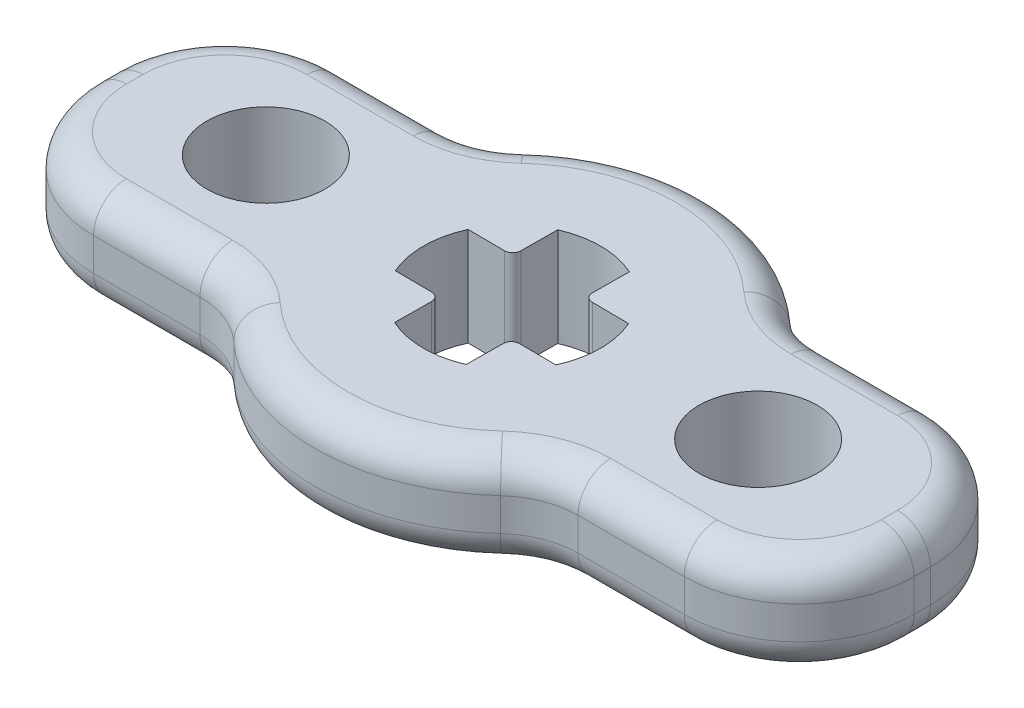
SolidWorks part; units mm, degrees
note: The reader was unsure of these and kept them because the rebuilt part matched: shared geometry of "Sketch1<3>".
ref_plane "Front Plane" through (0, 0, 0) normal (0, 0, 1) x (1, 0, 0)
ref_plane "Top Plane" through (0, 0, 0) normal (0, 1, 0) x (1, 0, 0)
ref_plane "Right Plane" through (0, 0, 0) normal (1, 0, 0) x (0, 0, -1)
sketch "Sketch1" plane through (0, 0, 0) normal (0, 1, 0) x (1, 0, 0)
  line L1 (-12.5, -3.75) -> (12.5, -3.75)
  line L2 (-12.5, -3.75) -> (-12.5, 3.75)
  line L3 (-12.5, 3.75) -> (12.5, 3.75)
  line L4 (12.5, -3.75) -> (12.5, 3.75)
  line L5 (-12.5, -3.75) -> (12.5, 3.75) construction
  line L6 (-12.5, 3.75) -> (12.5, -3.75) construction
  line L8 (-5, -3.75) -> (-5, 3.75)
  line L10 (5, -3.75) -> (5, 3.75)
  line L11 (3.5787, -3.75) -> (6.4358, 3.75) construction
  line L12 (3.5642, 3.75) -> (6.4213, -3.75) construction
  line L32 (-5, 3.75) -> (5, 3.75) construction
  line L33 (0.7935, -0.8065) -> (0.7816, -2.2692) construction
  line L34 (-0.8183, -2.2562) -> (-0.8065, -0.7935) construction
  line L35 (-0.8065, -0.7935) -> (-2.2692, -0.7816) construction
  line L36 (-0.7935, 0.8065) -> (-0.7816, 2.2692) construction
  line L37 (-2.2562, 0.8183) -> (-0.7935, 0.8065) construction
  line L38 (2.2562, -0.8183) -> (0.7935, -0.8065) construction
  line L39 (0.8065, 0.7935) -> (2.2692, 0.7816) construction
  line L40 (0.8183, 2.2562) -> (0.8065, 0.7935) construction
  line L41 (2.2562, -0.8183) -> (0.7935, -0.8065)
  line L42 (0.8065, 0.7935) -> (2.2692, 0.7816)
  line L43 (0.8183, 2.2562) -> (0.8065, 0.7935)
  line L44 (-2.2562, 0.8183) -> (-0.7935, 0.8065)
  line L45 (-0.7935, 0.8065) -> (-0.7816, 2.2692)
  line L46 (-0.8065, -0.7935) -> (-2.2692, -0.7816)
  line L47 (-0.8183, -2.2562) -> (-0.8065, -0.7935)
  line L48 (0.7935, -0.8065) -> (0.7816, -2.2692)
  line L49 (2.4568, -1.1199) -> (1.091, -1.1089)
  line L50 (1.091, -1.1089) -> (1.08, -2.4746)
  line L51 (-1.1199, -2.4568) -> (-1.1089, -1.091)
  line L52 (-1.1089, -1.091) -> (-2.4746, -1.08)
  line L53 (-2.4568, 1.1199) -> (-1.091, 1.1089)
  line L54 (-1.091, 1.1089) -> (-1.08, 2.4746)
  line L55 (1.1199, 2.4568) -> (1.1089, 1.091)
  line L56 (1.1089, 1.091) -> (2.4746, 1.08)
  circle A1 centre (0, 0) radius 3
  arc A3 (-0.8183, -2.2562) -> (0.7816, -2.2692) centre (0, 0) ccw construction
  arc A4 (-2.2562, 0.8183) -> (-2.2692, -0.7816) centre (0, 0) ccw construction
  arc A5 (2.2562, -0.8183) -> (2.2692, 0.7816) centre (0, 0) ccw construction
  arc A6 (0.8183, 2.2562) -> (-0.7816, 2.2692) centre (0, 0) ccw construction
  arc A7 (2.2562, -0.8183) -> (2.2692, 0.7816) centre (0, 0) ccw
  arc A8 (0.8183, 2.2562) -> (-0.7816, 2.2692) centre (0, 0) ccw
  arc A9 (-2.2562, 0.8183) -> (-2.2692, -0.7816) centre (0, 0) ccw
  arc A10 (-0.8183, -2.2562) -> (0.7816, -2.2692) centre (0, 0) ccw
  arc A11 (-1.1199, -2.4568) -> (1.08, -2.4746) centre (0, 0) ccw
  arc A12 (-2.4568, 1.1199) -> (-2.4746, -1.08) centre (0, 0) ccw
  arc A13 (1.1199, 2.4568) -> (-1.08, 2.4746) centre (0, 0) ccw
  arc A14 (2.4568, -1.1199) -> (2.4746, 1.08) centre (0, 0) ccw
  point P2 (0, 3.75)
  dimension "D1" = 6
  dimension "D2" = 0.3
  dimension "D3" = 10
  dimension "D4" = 25
  dimension "D5" = 7.5
extrude "Boss-Extrude1" add sketch "Sketch1" along normal blind 3
extrude "Cut-Extrude2" cut sketch "Sketch1<3>" along normal through all contours L49 A14 L56 L55 A13 L54 L53 A12 L52 L51 A11 L50 A10 L47 L46 A9 L44 L45 A8 L43 L42 A7 L41 L48 | L47 A10 L48 L41 A7 L42 L43 A8 L45 L44 A9 L46
sketch "Sketch1<3>" plane through (0, 0, 0) normal (0, 1, 0) x (1, 0, 0) same geometry as "Sketch1"
sketch "Sketch4" plane through (0, 0, 0) normal (0, 1, 0) x (1, 0, 0)
  line L0 (5, -3.75) -> (5, 3.75) construction
  line L1 (-5, -3.75) -> (-5, 3.75) construction
  line L2 (5, -3.75) -> (5, 3.75)
  line L3 (-5, -3.75) -> (-5, 3.75)
  line L4 (-12.5, -3.75) -> (12.5, -3.75)
  line L5 (12.5, -3.75) -> (12.5, 3.75)
  line L6 (12.5, 3.75) -> (-12.5, 3.75)
  line L7 (-12.5, 3.75) -> (-12.5, -3.75)
  line L8 (-12.5, -3.75) -> (12.5, -3.75)
  line L9 (12.5, -3.75) -> (12.5, 3.75)
  line L10 (12.5, 3.75) -> (-12.5, 3.75)
  line L11 (-12.5, 3.75) -> (-12.5, -3.75)
  line L16 (-1.091, 1.1089) -> (-2.4568, 1.1199)
  line L17 (-1.08, 2.4746) -> (-1.091, 1.1089)
  line L18 (1.1089, 1.091) -> (1.1199, 2.4568)
  line L19 (2.4746, 1.08) -> (1.1089, 1.091)
  line L20 (1.091, -1.1089) -> (2.4568, -1.1199)
  line L21 (1.08, -2.4746) -> (1.091, -1.1089)
  line L22 (-1.1089, -1.091) -> (-1.1199, -2.4568)
  line L23 (-2.4746, -1.08) -> (-1.1089, -1.091)
  line L24 (-1.091, 1.1089) -> (-2.4568, 1.1199)
  line L25 (-1.08, 2.4746) -> (-1.091, 1.1089)
  line L26 (1.1089, 1.091) -> (1.1199, 2.4568)
  line L27 (2.4746, 1.08) -> (1.1089, 1.091)
  line L28 (1.091, -1.1089) -> (2.4568, -1.1199)
  line L29 (1.08, -2.4746) -> (1.091, -1.1089)
  line L30 (-1.1089, -1.091) -> (-1.1199, -2.4568)
  line L31 (-2.4746, -1.08) -> (-1.1089, -1.091)
  line L32 (0.7935, -0.8065) -> (2.2562, -0.8183)
  line L33 (2.2692, 0.7816) -> (0.8065, 0.7935)
  line L34 (0.8065, 0.7935) -> (0.8183, 2.2562)
  line L35 (-0.7816, 2.2692) -> (-0.7935, 0.8065)
  line L36 (-0.7935, 0.8065) -> (-2.2562, 0.8183)
  line L37 (-2.2692, -0.7816) -> (-0.8065, -0.7935)
  line L38 (-0.8065, -0.7935) -> (-0.8183, -2.2562)
  line L39 (0.7816, -2.2692) -> (0.7935, -0.8065)
  line L40 (0.7935, -0.8065) -> (2.2562, -0.8183)
  line L41 (2.2692, 0.7816) -> (0.8065, 0.7935)
  line L42 (0.8065, 0.7935) -> (0.8183, 2.2562)
  line L43 (-0.7816, 2.2692) -> (-0.7935, 0.8065)
  line L44 (-0.7935, 0.8065) -> (-2.2562, 0.8183)
  line L45 (-2.2692, -0.7816) -> (-0.8065, -0.7935)
  line L46 (-0.8065, -0.7935) -> (-0.8183, -2.2562)
  line L47 (0.7816, -2.2692) -> (0.7935, -0.8065)
  circle A0 centre (0, 0) radius 6
  circle A2 centre (0, 0) radius 3
  circle A3 centre (0, 0) radius 3
  arc A7 (1.1199, 2.4568) -> (-1.08, 2.4746) centre (0, 0) ccw
  arc A8 (2.4568, -1.1199) -> (2.4746, 1.08) centre (0, 0) ccw
  arc A9 (-1.1199, -2.4568) -> (1.08, -2.4746) centre (0, 0) ccw
  arc A10 (-2.4568, 1.1199) -> (-2.4746, -1.08) centre (0, 0) ccw
  arc A11 (1.1199, 2.4568) -> (-1.08, 2.4746) centre (0, 0) ccw
  arc A12 (2.4568, -1.1199) -> (2.4746, 1.08) centre (0, 0) ccw
  arc A13 (-1.1199, -2.4568) -> (1.08, -2.4746) centre (0, 0) ccw
  arc A14 (-2.4568, 1.1199) -> (-2.4746, -1.08) centre (0, 0) ccw
  arc A15 (2.2562, -0.8183) -> (2.2692, 0.7816) centre (0, 0) ccw
  arc A16 (0.8183, 2.2562) -> (-0.7816, 2.2692) centre (0, 0) ccw
  arc A17 (-2.2562, 0.8183) -> (-2.2692, -0.7816) centre (0, 0) ccw
  arc A18 (-0.8183, -2.2562) -> (0.7816, -2.2692) centre (0, 0) ccw
  arc A19 (2.2562, -0.8183) -> (2.2692, 0.7816) centre (0, 0) ccw
  arc A20 (0.8183, 2.2562) -> (-0.7816, 2.2692) centre (0, 0) ccw
  arc A21 (-2.2562, 0.8183) -> (-2.2692, -0.7816) centre (0, 0) ccw
  arc A22 (-0.8183, -2.2562) -> (0.7816, -2.2692) centre (0, 0) ccw
  dimension "D1" = 12
  dimension "D2" = 0
  dimension "D3" = 0
  dimension "D4" = 0
  dimension "D5" = 0
extrude "Boss-Extrude2" add sketch "Sketch4" along normal up to surface (3 mm away) contours L10 A0 | L8 A0 up to face at (0, 3, 0)
fillet "Fillet8" radius 2.5 4 edges at (-4.6837, 1.5, 3.75) (4.6837, 1.5, 3.75) (4.6837, 1.5, -3.75) (-4.6837, 1.5, -3.75)
fillet "Fillet4" radius 3.5 4 edges at (12.5, 1.5, -3.75) (12.5, 1.5, 3.75) (-12.5, 1.5, 3.75) (-12.5, 1.5, -3.75)
hole_wizard "M3 Clearance Hole1" positions "Sketch2" profile "Sketch3" hole size "M3" standard "ANSI Metric" end condition through all
sketch "Sketch2" plane through (0, 0, 0) normal (0, 1, 0) x (1, 0, 0)
  line L0 (-7.5, 0) -> (7.5, 0)
  line L2 (12.5, -0.25) -> (12.5, 0.25) construction
  point P0 (-7.5, 0)
  point P2 (7.5, 0)
  point P26 (0, 0)
  dimension "D1" = 5
sketch "Sketch3" plane through (-7.5, 0, 0) normal (1, 0, 0) x (0, 0, -1)
  line L0 (0, 0) -> (0, 3)
  line L1 (0, 3) -> (1.8, 3)
  line L2 (1.8, 3) -> (1.8, 0)
  line L5 (1.8, 0) -> (0, 0)
  line L11 (0, -6.35) -> (0, 107.95) construction
  dimension "Thru Hole Dia." = 3.6
  dimension "Thru Hole Depth" = 3
fillet "Fillet6" radius 1 32 edges at (-11.4749, 3, 2.7249) (-7.3804, 3, 3.75) (7.3804, 3, 3.75) (11.4749, 3, 2.7249) (11.4749, 3, -2.7249) (7.3804, 3, -3.75) (-7.3804, 3, -3.75) (-11.4749, 3, -2.7249) (-11.4749, 0, 2.7249) (7.3804, 0, 3.75) (-7.3804, 0, 3.75) (11.4749, 0, 2.7249) (11.4749, 0, -2.7249) (7.3804, 0, -3.75) (-7.3804, 0, -3.75) (-11.4749, 0, -2.7249) (12.5, 3, 0) (12.5, 0, 0) (-12.5, 3, 0) (-12.5, 0, 0) (-4.8514, 3, 3.9213) (0, 3, 6) (0, 0, 6) (4.8514, 3, 3.9213) (4.8514, 3, -3.9213) (0, 3, -6) (0, 0, -6) (-4.8514, 3, -3.9213) (-4.8514, 0, 3.9213) (4.8514, 0, 3.9213) (4.8514, 0, -3.9213) (-4.8514, 0, -3.9213)
fillet "Fillet7" radius 0.25 4 edges at (-1.1089, 1.5, 1.091) (1.091, 1.5, 1.1089) (1.1089, 1.5, -1.091) (-1.091, 1.5, -1.1089)
